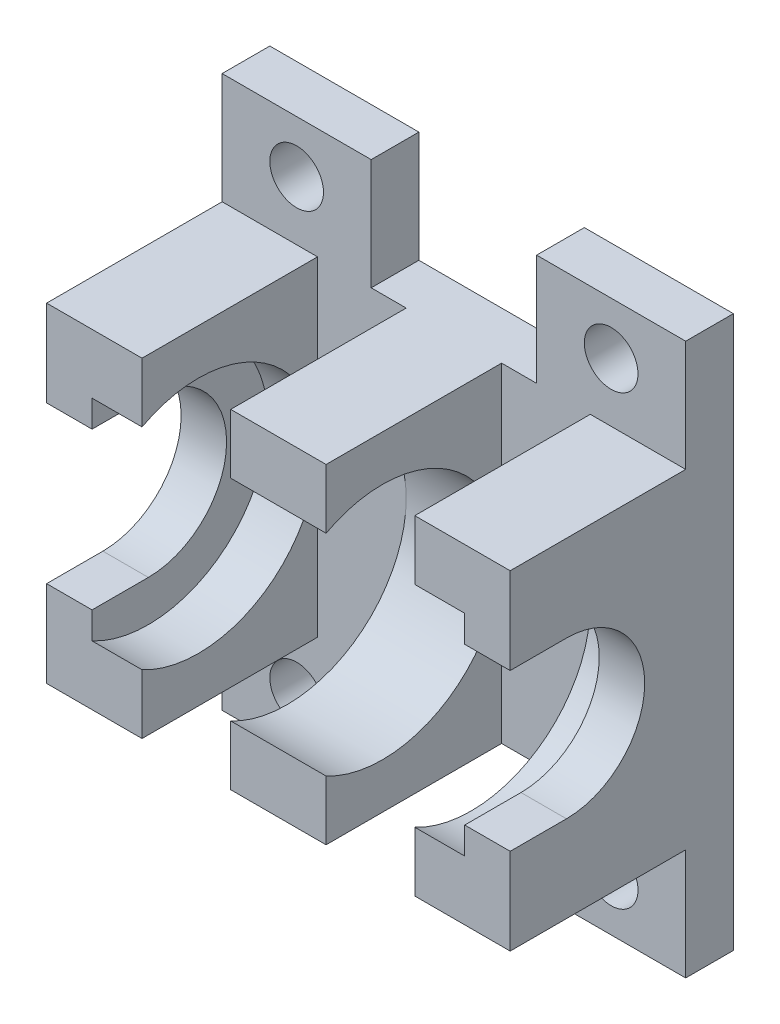
SolidWorks part; units mm, degrees
ref_plane "Piano frontale" through (0, 0, 0) normal (0, 0, 1) x (1, 0, 0)
ref_plane "Piano superiore" through (0, 0, 0) normal (0, 1, 0) x (1, 0, 0)
ref_plane "Piano destro" through (0, 0, 0) normal (1, 0, 0) x (0, 0, -1)
sketch "Schizzo1" plane through (0, 0, 0) normal (0, 0, 1) x (1, 0, 0)
  line L0 (0, 18.5) -> (0, -18.5) construction
  line L1 (-15.55, 11.05) -> (-15.55, 18.5)
  line L2 (15.55, -11.05) -> (15.55, 11.05)
  line L3 (-15.55, 18.5) -> (-5.55, 18.5)
  line L4 (-15.55, -11.05) -> (-15.55, 11.05)
  line L5 (15.55, -11.05) -> (-15.55, 11.05) construction
  line L6 (15.55, 11.05) -> (-15.55, -11.05) construction
  line L7 (-5.55, 18.5) -> (-5.55, 11.05)
  line L8 (-5.55, 11.05) -> (5.55, 11.05)
  line L9 (-15.55, 11.05) -> (-5.55, 11.05) construction
  line L10 (-10.55, 11.05) -> (-10.55, 18.5) construction
  line L11 (5.55, 18.5) -> (5.55, 11.05)
  line L12 (15.55, 18.5) -> (5.55, 18.5)
  line L13 (15.55, 11.05) -> (15.55, 18.5)
  line L14 (15.55, -11.05) -> (15.55, -18.5)
  line L15 (15.55, -18.5) -> (5.55, -18.5)
  line L16 (5.55, -18.5) -> (5.55, -11.05)
  line L17 (-15.55, 0) -> (15.55, 0) construction
  line L18 (-5.55, -11.05) -> (5.55, -11.05)
  line L19 (-5.55, -18.5) -> (-5.55, -11.05)
  line L20 (-15.55, -18.5) -> (-5.55, -18.5)
  line L21 (-15.55, -11.05) -> (-15.55, -18.5)
  circle A0 centre (-10.55, 15) radius 1.8
  circle A1 centre (10.55, 15) radius 1.8
  circle A2 centre (10.55, -15) radius 1.8
  circle A3 centre (-10.55, -15) radius 1.8
  point P0 (0, 0)
  point P21 (0, 11.05)
  dimension "D5" = 3.5
  dimension "D6" = 3.6
  dimension "D1" = 22.1
  dimension "D2" = 31.1
  dimension "D3" = 10
  dimension "D4" = 7.45
extrude "Base" add sketch "Schizzo1" along normal blind 3.2
sketch "Schizzo2" plane through (0, 0, 3.2) normal (0, 0, 1) x (1, 0, 0)
  line L0 (-15.55, 18.5) -> (-15.55, -18.5) construction
  line L1 (-9.15, -11.05) -> (-3.2, -11.05) construction
  line L2 (3.2, -11.05) -> (9.15, -11.05) construction
  line L3 (-9.15, 11.05) -> (-3.2, 11.05) construction
  line L4 (-15.55, -11.05) -> (-9.15, -11.05)
  line L5 (-15.55, -11.05) -> (-15.55, 11.05)
  line L6 (-15.55, 11.05) -> (-9.15, 11.05)
  line L7 (-9.15, -11.05) -> (-9.15, 11.05)
  line L8 (5.55, 11.05) -> (-5.55, 11.05) construction
  line L9 (-3.2, -11.05) -> (3.2, -11.05)
  line L10 (-3.2, -11.05) -> (-3.2, 11.05)
  line L11 (-3.2, 11.05) -> (3.2, 11.05)
  line L12 (3.2, -11.05) -> (3.2, 11.05)
  line L13 (3.2, 11.05) -> (9.15, 11.05) construction
  line L15 (-3.2, -11.05) -> (3.2, 11.05) construction
  line L16 (-3.2, 11.05) -> (3.2, -11.05) construction
  line L17 (15.55, -18.5) -> (15.55, 18.5) construction
  line L18 (15.55, 11.05) -> (9.15, 11.05)
  line L19 (15.55, 11.05) -> (15.55, -11.05)
  line L20 (15.55, -11.05) -> (9.15, -11.05)
  line L21 (9.15, 11.05) -> (9.15, -11.05)
  point P6 (0, 0)
  dimension "D1" = 6.4
extrude "Stand-off" add sketch "Schizzo2" along normal blind 11.775
sketch "Schizzo3" plane through (0, 0, 0) normal (1, 0, 0) x (0, 0, -1)
  line L0 (-14.975, 11.05) -> (-14.975, -11.05) construction
  line L1 (-14.975, 11.05) -> (-14.975, -11.05) construction
  line L2 (-11.2, 0) -> (-14.975, 0) construction
  line L5 (-3.2, 11.05) -> (-3.2, -11.05) construction
  line L6 (-11.2, 0) -> (-3.2, 0) construction
  line L7 (-3.2, 11.05) -> (-3.2, -11.05) construction
  circle A0 centre (-11.2, 0) radius 8
  dimension "D1" = 16
extrude "Bearing slot" cut sketch "Schizzo3" against normal mid plane 25
sketch "Schizzo4" plane through (-15.55, 0, 0) normal (-1, 0, 0) x (0, 0, 1)
  line L0 (11.2, 5.25) -> (11.2, -5.25) construction
  line L1 (11.2, 5.25) -> (14.975, 5.25)
  line L2 (14.975, 11.05) -> (14.975, -11.05) construction
  line L4 (14.975, 5.25) -> (14.975, -5.25)
  line L5 (14.975, -5.25) -> (11.2, -5.25)
  arc A0 (14.975, 7.0533) -> (3.2, 0) centre (11.2, 0) ccw construction
  arc A1 (3.2, 0) -> (14.975, -7.0533) centre (11.2, 0) ccw construction
  arc A2 (14.975, 7.0533) -> (3.2, 0) centre (11.2, 0) ccw construction
  arc A4 (3.2, 0) -> (14.975, -7.0533) centre (11.2, 0) ccw construction
  arc A6 (11.2, 5.25) -> (11.2, -5.25) centre (11.2, 0) ccw
  dimension "D1" = 10.5
extrude "Shaft holes" cut sketch "Schizzo4" against normal up to surface (31.1 mm away) contours L5 A6 L1 L4 up to face at (15.55, 0, 5.3438)
ref_axis "Bearing axis" through (-3.2, 0, 11.2) along (1, 0, 0)
